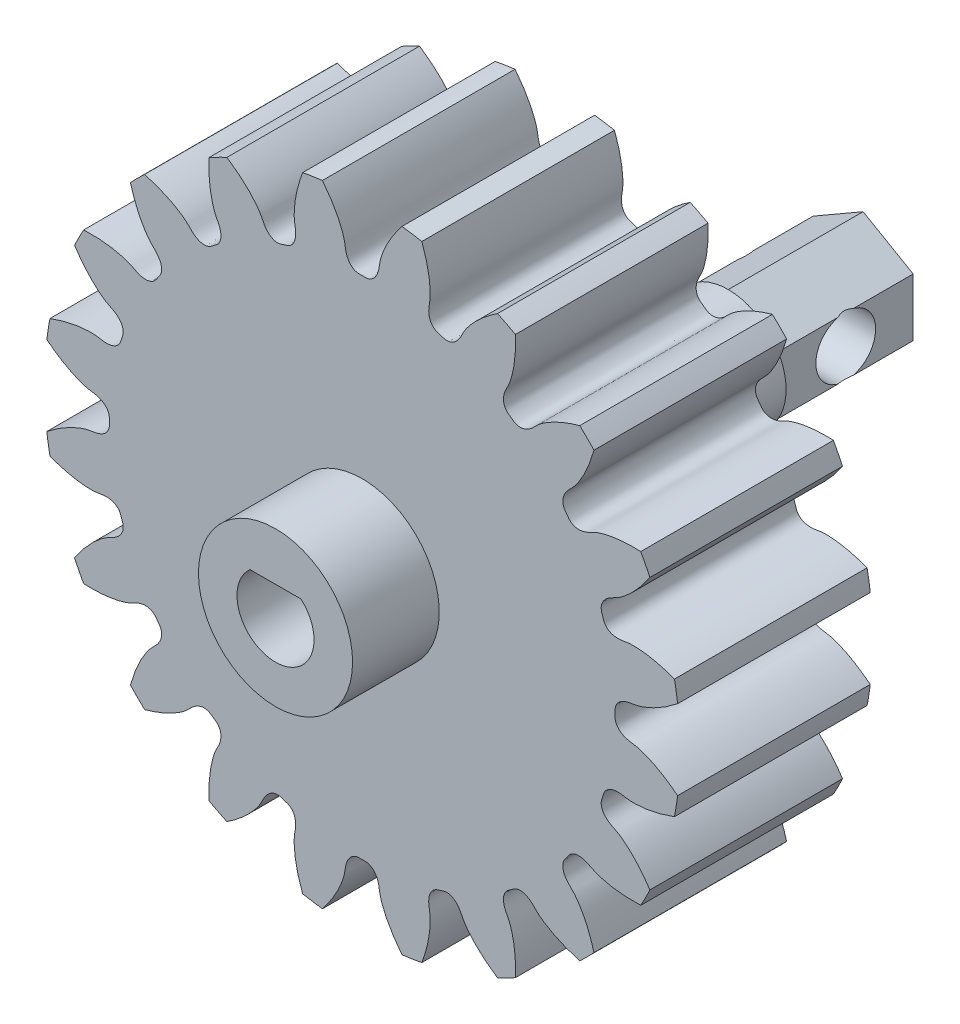
SolidWorks part; units mm, degrees
ref_plane "Front Plane" through (0, 0, 0) normal (0, 0, 1) x (1, 0, 0)
ref_plane "Top Plane" through (0, 0, 0) normal (0, 1, 0) x (1, 0, 0)
ref_plane "Right Plane" through (0, 0, 0) normal (1, 0, 0) x (0, 0, -1)
ref_axis "Axis1" through (0, 0, 55) along (0, 0, -1)
sketch "SketchRevolveSpurAssembly01Pinion" plane through (0, 0, 0) normal (1, 0, 0) x (0, 0, -1)
  line L0 (0, 0) -> (1, 0) construction
  line L1 (-5, 0) -> (-5, 16.5)
  line L2 (-5, 16.5) -> (5, 16.5)
  line L3 (5, 16.5) -> (5, 0)
  line L4 (5, 0) -> (-5, 0)
  dimension "Side1" = 5
  dimension "OutsideRadius" = 16.5
  dimension "Side2" = 5
revolve "SpurAssembly01Pinion" add sketch "SketchRevolveSpurAssembly01Pinion" angle 360 about L0
sketch "SketchToothSpurAssembly01Pinion" plane through (0, 0, 0) normal (0, 0, 1) x (1, 0, 0)
  arc A0 (16.4388, 2.1204) -> (16.4388, -2.1204) centre (0, 0) cw
  spline S0 degree 3 poles (16.4388, -2.1204) (16.3062, -2.0126) (16.1079, -1.8609) (15.8417, -1.6767) (15.6549, -1.5557) (15.4759, -1.4476) (15.3054, -1.3516) (15.1441, -1.2672) (14.9923, -1.1937) (14.8506, -1.1305) (14.7196, -1.0767) (14.5996, -1.0318) (14.491, -0.9949) (14.3942, -0.9653) (14.3096, -0.9423) (14.2375, -0.925) (14.178, -0.9126) (14.0492, -0.8903) (13.9123, -0.8782) (13.7697, -0.8427) (13.6956, -0.8206) (13.6244, -0.795) (13.5557, -0.7654) (13.4893, -0.7311) (13.4248, -0.6913) (13.3623, -0.6446) (13.3021, -0.5892) (13.2452, -0.523) (13.1943, -0.4439) (13.1533, -0.3509) (13.1303, -0.2534) (13.1208, -0.135) (13.1277, 0) (13.1208, 0.135) (13.1303, 0.2534) (13.1533, 0.3509) (13.1943, 0.4439) (13.2452, 0.523) (13.3021, 0.5892) (13.3623, 0.6446) (13.4248, 0.6913) (13.4893, 0.7311) (13.5557, 0.7654) (13.6244, 0.795) (13.6956, 0.8206) (13.7697, 0.8427) (13.9123, 0.8782) (14.0492, 0.8903) (14.178, 0.9126) (14.2375, 0.925) (14.3096, 0.9423) (14.3942, 0.9653) (14.491, 0.9949) (14.5996, 1.0318) (14.7196, 1.0767) (14.8506, 1.1305) (14.9923, 1.1937) (15.1441, 1.2672) (15.3054, 1.3516) (15.4759, 1.4476) (15.6549, 1.5557) (15.8417, 1.6767) (16.1079, 1.8609) (16.3062, 2.0126) (16.4388, 2.1204) knots 0 0 0 0 0.061423 0.08971 0.11638 0.141434 0.164872 0.186693 0.206898 0.225486 0.242459 0.257814 0.271554 0.283677 0.294183 0.303073 0.310347 0.316004 0.350077 0.359568 0.368803 0.377844 0.386769 0.395676 0.404689 0.413963 0.423683 0.434051 0.445256 0.457401 0.47042 0.481067 0.5 0.518933 0.52958 0.542599 0.554744 0.565949 0.576317 0.586037 0.595311 0.604324 0.613231 0.622156 0.631197 0.640432 0.649923 0.683996 0.689653 0.696927 0.705817 0.716323 0.728446 0.742186 0.757541 0.774514 0.793102 0.813307 0.835128 0.858566 0.88362 0.91029 0.938577 1 1 1 1
extrude "ToothExtrudeCutSpurAssembly01Pinion" cut sketch "SketchToothSpurAssembly01Pinion" against normal blind 5 and the other way blind 5
pattern_circular "PatternSpurAssembly01Pinion" count 20 every 18 about axis through (0, 0, 55) along (0, 0, -1) of "ToothExtrudeCutSpurAssembly01Pinion"
sketch "AuxiliarySketchSpurAssembly01Pinion" plane through (0, 0, 0) normal (0, 0, 1) x (1, 0, 0)
  circle A0 centre (0, 0) radius 15 construction
  circle A1 centre (0, 0) radius 14.0954 construction
  circle A2 centre (0, 0) radius 14.1048 construction
  circle A3 centre (0, 0) radius 16.5 construction
  circle A4 centre (0, 0) radius 13.125 construction
  dimension "PitchDiameter" = 30
  dimension "BaseDiameter" = 28.1908
  dimension "FormDiameter" = 28.2095
  dimension "MajorDiameter" = 33
  dimension "MinorDiameter" = 26.25
sketch "Sketch2" plane through (0, 0, -5) normal (0, 0, -1) x (-1, 0, 0)
  circle A0 centre (0, 0) radius 3
extrude "Boss-Extrude1" add sketch "Sketch2" along normal blind 9
sketch "Sketch3" plane through (0, 0, -14) normal (0, 0, -1) x (-1, 0, 0)
  line L0 (0, 3) -> (-2.5981, 1.5)
  line L1 (-2.5981, 1.5) -> (-2.5981, -1.5)
  line L2 (0, -3) -> (0, 3) construction
  line L3 (-2.5981, -1.5) -> (2.5981, 1.5) construction
  line L4 (2.5981, -1.5) -> (-2.5981, 1.5) construction
  line L5 (-2.5981, -1.5) -> (0, -3)
  line L6 (0, -3) -> (2.5981, -1.5)
  line L7 (2.5981, -1.5) -> (2.5981, 1.5)
  line L8 (2.5981, 1.5) -> (0, 3)
  circle A0 centre (0, 0) radius 3 construction
  point P11 (0, 0)
  point P15 (0, 0)
  point P18 (0, 0)
extrude "Boss-Extrude2" add sketch "Sketch3" along normal blind 7
sketch "Sketch4" plane through (2.5981, 0, 0) normal (1, 0, 0) x (0, 0, -1)
  line L0 (14, 1.5) -> (21, -1.5) construction
  circle A0 centre (17.5, 0) radius 1.55
extrude "Cut-Extrude3" cut sketch "Sketch4" against normal up to surface (5.1962 mm away) up to face at (-2.5981, 0, -17.5)
sketch "Sketch5" plane through (0, 0, 5) normal (0, 0, 1) x (1, 0, 0)
  circle A0 centre (0, 0) radius 4
extrude "Boss-Extrude3" add sketch "Sketch5" along normal blind 4.5
sketch "Sketch6" plane through (0, 0, 9.5) normal (0, 0, 1) x (1, 0, 0)
  line L0 (0, 0) -> (0, 1.5) construction
  line L1 (-1.3229, 1.5) -> (1.3229, 1.5)
  circle A0 centre (0, 0) radius 2 construction
  arc A1 (1.3229, 1.5) -> (-1.3229, 1.5) centre (0, 0) cw
  point P7 (0, 1.5)
extrude "Cut-Extrude4" cut sketch "Sketch6" against normal blind 8
